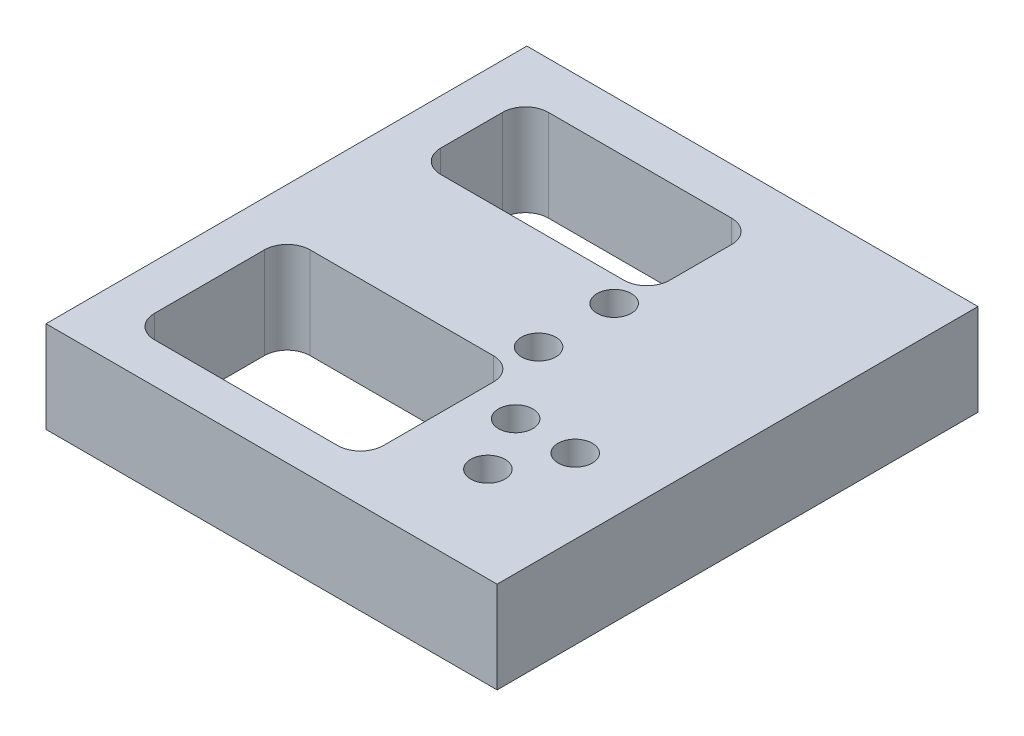
SolidWorks part; units mm, degrees
material "K110"
ref_plane "Front Plane" through (0, 0, 0) normal (0, 0, 1) x (1, 0, 0)
ref_plane "Top Plane" through (0, 0, 0) normal (0, 1, 0) x (1, 0, 0)
ref_plane "Right Plane" through (0, 0, 0) normal (1, 0, 0) x (0, 0, -1)
sketch "Sketch1" plane through (0, 0, 0) normal (0, 1, 0) x (1, 0, 0)
  line L1 (-98.5, -105) -> (98.5, -105)
  line L2 (-98.5, -105) -> (-98.5, 105)
  line L3 (-98.5, 105) -> (98.5, 105)
  line L4 (98.5, -105) -> (98.5, 105)
  line L5 (-98.5, -105) -> (98.5, 105) construction
  line L6 (-98.5, 105) -> (98.5, -105) construction
  point P0 (0, 0)
  dimension "D1" = 210
  dimension "D2" = 197
extrude "Boss-Extrude1" add sketch "Sketch1" against normal blind 40
sketch "Sketch2" plane through (0, 0, 0) normal (0, 1, 0) x (1, 0, 0)
  line L0 (-29.25, -63.53) -> (-29.25, -47.4) construction
  line L1 (-32.25, -44.4) -> (-36.25, -44.4) construction
  line L2 (-42.25, -38.4) -> (-42.25, -32.27) construction
  line L3 (-42.25, -32.27) -> (-61.37, -32.27) construction
  line L12 (-64.37, -35.27) -> (-64.37, -71.53) construction
  line L13 (-61.37, -74.53) -> (3.88, -74.53) construction
  line L14 (-17.25, -47.4) -> (-17.25, -63.53) construction
  line L15 (-10.25, -44.4) -> (-14.25, -44.4) construction
  line L16 (-4.25, -32.27) -> (-4.25, -38.4) construction
  line L17 (3.88, -32.27) -> (-4.25, -32.27) construction
  line L18 (6.88, -71.53) -> (6.88, -35.27) construction
  line L19 (-29.25, -63.53) -> (-29.25, -47.4)
  line L20 (-32.25, -44.4) -> (-36.25, -44.4)
  line L21 (-42.25, -38.4) -> (-42.25, -32.27)
  line L22 (-42.25, -32.27) -> (-61.37, -32.27)
  line L23 (-64.37, -35.27) -> (-64.37, -71.53)
  line L24 (-61.37, -74.53) -> (3.88, -74.53)
  line L25 (-17.25, -47.4) -> (-17.25, -63.53)
  line L26 (-10.25, -44.4) -> (-14.25, -44.4)
  line L27 (-4.25, -32.27) -> (-4.25, -38.4)
  line L28 (3.88, -32.27) -> (-4.25, -32.27)
  line L29 (6.88, -71.53) -> (6.88, -35.27)
  line L30 (-4.25, 47.73) -> (3.88, 47.73) construction
  line L31 (-4.25, 69.53) -> (-4.25, 47.73) construction
  line L32 (-42.25, 69.53) -> (-4.25, 69.53) construction
  line L33 (-42.25, 47.73) -> (-42.25, 69.53) construction
  line L34 (-61.37, 47.73) -> (-42.25, 47.73) construction
  line L35 (-64.37, 71.53) -> (-64.37, 50.73) construction
  line L36 (3.88, 74.53) -> (-61.37, 74.53) construction
  line L37 (6.88, 50.73) -> (6.88, 71.53) construction
  line L38 (-4.25, 47.73) -> (3.88, 47.73)
  line L39 (-4.25, 69.53) -> (-4.25, 47.73)
  line L40 (-42.25, 69.53) -> (-4.25, 69.53)
  line L41 (-42.25, 47.73) -> (-42.25, 69.53)
  line L42 (-61.37, 47.73) -> (-42.25, 47.73)
  line L43 (-64.37, 71.53) -> (-64.37, 50.73)
  line L44 (3.88, 74.53) -> (-61.37, 74.53)
  line L45 (6.88, 50.73) -> (6.88, 71.53)
  arc A0 (-29.25, -47.4) -> (-32.25, -44.4) centre (-32.25, -47.4) ccw construction
  arc A1 (-42.25, -38.4) -> (-36.25, -44.4) centre (-36.25, -38.4) ccw construction
  arc A2 (-61.37, -32.27) -> (-64.37, -35.27) centre (-61.37, -35.27) ccw construction
  arc A3 (-64.37, -71.53) -> (-61.37, -74.53) centre (-61.37, -71.53) ccw construction
  arc A4 (3.88, -74.53) -> (6.88, -71.53) centre (3.88, -71.53) ccw construction
  arc A5 (-29.25, -63.53) -> (-17.25, -63.53) centre (-23.25, -63.53) ccw construction
  arc A6 (-14.25, -44.4) -> (-17.25, -47.4) centre (-14.25, -47.4) ccw construction
  arc A7 (-10.25, -44.4) -> (-4.25, -38.4) centre (-10.25, -38.4) ccw construction
  arc A8 (6.88, -35.27) -> (3.88, -32.27) centre (3.88, -35.27) ccw construction
  arc A9 (-29.25, -47.4) -> (-32.25, -44.4) centre (-32.25, -47.4) ccw
  arc A10 (-42.25, -38.4) -> (-36.25, -44.4) centre (-36.25, -38.4) ccw
  arc A11 (-61.37, -32.27) -> (-64.37, -35.27) centre (-61.37, -35.27) ccw
  arc A12 (-64.37, -71.53) -> (-61.37, -74.53) centre (-61.37, -71.53) ccw
  arc A13 (3.88, -74.53) -> (6.88, -71.53) centre (3.88, -71.53) ccw
  arc A14 (-29.25, -63.53) -> (-17.25, -63.53) centre (-23.25, -63.53) ccw
  arc A15 (-14.25, -44.4) -> (-17.25, -47.4) centre (-14.25, -47.4) ccw
  arc A16 (-10.25, -44.4) -> (-4.25, -38.4) centre (-10.25, -38.4) ccw
  arc A17 (6.88, -35.27) -> (3.88, -32.27) centre (3.88, -35.27) ccw
  circle A18 centre (53, -63.53) radius 2.5 construction
  circle A19 centre (66, -38.4) radius 2.5 construction
  circle A20 centre (40, -38.4) radius 2.5 construction
  circle A21 centre (17.88, -6.27) radius 2.5 construction
  circle A22 centre (17.88, 26.73) radius 2.5 construction
  arc A23 (3.88, 47.73) -> (6.88, 50.73) centre (3.88, 50.73) ccw construction
  arc A24 (-64.37, 50.73) -> (-61.37, 47.73) centre (-61.37, 50.73) ccw construction
  arc A25 (-61.37, 74.53) -> (-64.37, 71.53) centre (-61.37, 71.53) ccw construction
  arc A26 (6.88, 71.53) -> (3.88, 74.53) centre (3.88, 71.53) ccw construction
  circle A27 centre (53, -63.53) radius 2.5
  circle A28 centre (66, -38.4) radius 2.5
  circle A29 centre (40, -38.4) radius 2.5
  circle A30 centre (17.88, -6.27) radius 2.5
  circle A31 centre (17.88, 26.73) radius 2.5
  arc A32 (3.88, 47.73) -> (6.88, 50.73) centre (3.88, 50.73) ccw
  arc A33 (-64.37, 50.73) -> (-61.37, 47.73) centre (-61.37, 50.73) ccw
  arc A34 (-61.37, 74.53) -> (-64.37, 71.53) centre (-61.37, 71.53) ccw
  arc A35 (6.88, 71.53) -> (3.88, 74.53) centre (3.88, 71.53) ccw
sketch "Sketch3" plane through (0, 0, 0) normal (0, 1, 0) x (1, 0, 0)
  line L1 (-68.745, 84.63) -> (11.255, 84.63)
  line L2 (-78.745, 74.63) -> (-78.745, 47.63)
  line L3 (-68.745, 37.63) -> (11.255, 37.63)
  line L4 (21.255, 74.63) -> (21.255, 47.63)
  line L8 (-64.37, -53.4) -> (6.88, -53.4) construction
  line L9 (-68.745, -19.4) -> (11.255, -19.4)
  line L10 (-78.745, -29.4) -> (-78.745, -77.4)
  line L11 (-68.745, -87.4) -> (11.255, -87.4)
  line L12 (21.255, -29.4) -> (21.255, -77.4)
  line L13 (-64.37, -35.27) -> (-64.37, -71.53) construction
  line L14 (6.88, -71.53) -> (6.88, -35.27) construction
  line L15 (-28.745, -74.53) -> (-28.745, -19.4) construction
  line L16 (-61.37, -74.53) -> (3.88, -74.53) construction
  line L17 (-28.745, 84.63) -> (-28.745, 47.73) construction
  line L18 (-64.37, 61.13) -> (6.88, 61.13) construction
  line L19 (-64.37, 71.53) -> (-64.37, 50.73) construction
  line L20 (6.88, 50.73) -> (6.88, 71.53) construction
  arc A0 (-78.745, 47.63) -> (-68.745, 37.63) centre (-68.745, 47.63) ccw
  arc A1 (11.255, 37.63) -> (21.255, 47.63) centre (11.255, 47.63) ccw
  arc A2 (21.255, 74.63) -> (11.255, 84.63) centre (11.255, 74.63) ccw
  arc A3 (-68.745, 84.63) -> (-78.745, 74.63) centre (-68.745, 74.63) ccw
  circle A4 centre (17.88, 26.73) radius 7.5
  circle A5 centre (17.88, -6.27) radius 7.5
  circle A6 centre (53, -63.53) radius 7.5
  circle A7 centre (66, -38.4) radius 7.5
  circle A8 centre (40, -38.4) radius 7.5
  arc A9 (-78.745, -77.4) -> (-68.745, -87.4) centre (-68.745, -77.4) ccw
  arc A10 (11.255, -87.4) -> (21.255, -77.4) centre (11.255, -77.4) ccw
  arc A11 (21.255, -29.4) -> (11.255, -19.4) centre (11.255, -29.4) ccw
  arc A12 (-68.745, -19.4) -> (-78.745, -29.4) centre (-68.745, -29.4) ccw
  dimension "D5" = 10
  dimension "D6" = 15
  dimension "D11" = 10
  dimension "D2" = 100
  dimension "D3" = 47
  dimension "D7" = 68
  dimension "D8" = 100
extrude "Cut-Extrude2" cut sketch "Sketch3" against normal up to next
sketch "Sketch4" plane through (0, -40, 0) normal (0, -1, 0) x (1, 0, 0)
  circle A0 centre (17.88, -26.73) radius 9
  circle A1 centre (17.88, 6.27) radius 9
  circle A2 centre (40, 38.4) radius 9
  circle A3 centre (66, 38.4) radius 9
  circle A4 centre (53, 63.53) radius 9
  dimension "D1" = 18
extrude "Cut-Extrude3" cut sketch "Sketch4" against normal blind 5
